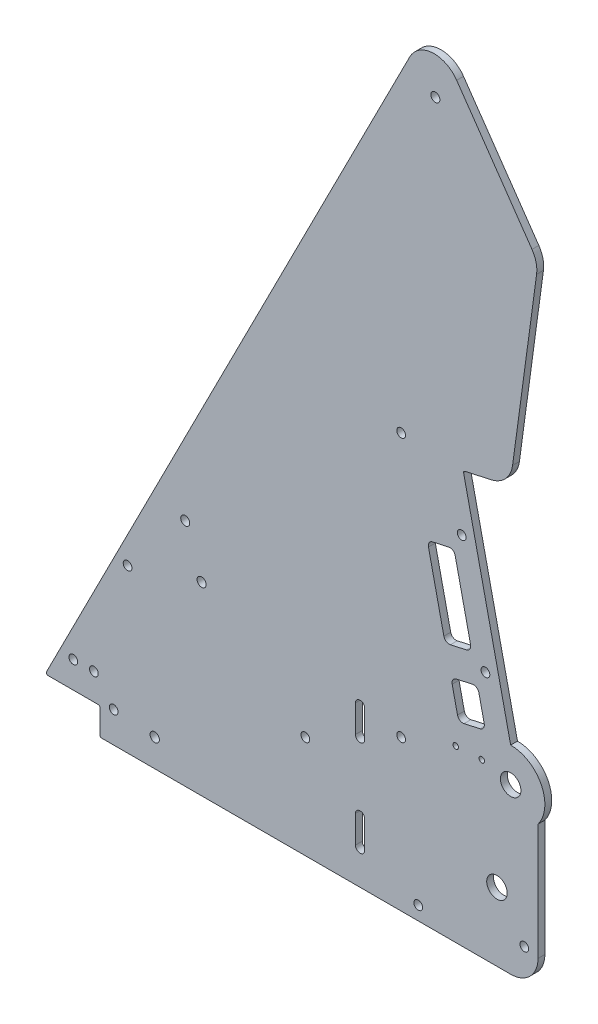
SolidWorks part; units mm, degrees
other "Markup1"
sketch "Sketch5"
ref_plane "Front Plane" through (0, 0, 0) normal (0, 0, 1) x (1, 0, 0)
ref_plane "Top Plane" through (0, 0, 0) normal (0, 1, 0) x (1, 0, 0)
ref_plane "Right Plane" through (0, 0, 0) normal (1, 0, 0) x (0, 0, -1)
sketch "Sketch1" plane through (0, 0, 0) normal (0, 0, 1) x (1, 0, 0)
  line L1 (228.6, -12.7) -> (228.6, 53.975)
  line L2 (178.7547, 351.4131) -> (0, 0)
  line L3 (228.6, 279.4) -> (178.7547, 351.4131)
  line L5 (0, 0) -> (25.4, 0)
  line L6 (25.4, 0) -> (25.4, -12.7)
  line L7 (25.4, -12.7) -> (228.6, -12.7)
  line L9 (215.9, 79.375) -> (193.9097, 178.5667)
  line L10 (193.9097, 178.5667) -> (215.6079, 183.377)
  line L11 (215.6079, 183.377) -> (228.6, 279.4)
  arc A0 (228.6, 53.975) -> (215.9, 79.375) centre (215.9, 63.5) ccw
  dimension "D7" = 12.7
  dimension "D8" = 76.2
  dimension "D10" = 31.75
  dimension "D2" = 292.1
  dimension "D3" = 25.4
  dimension "D4" = 215.9
  dimension "D5" = 394.2644
  dimension "D6" = 203.2
  dimension "D9" = 63.039
  dimension "D11" = 101.6
  dimension "D12" = 12.5
  dimension "D13" = 22.225
extrude "Boss-Extrude1" add sketch "Sketch1" along normal blind 3.175
sketch "Sketch2" plane through (0, 0, 3.175) normal (0, 0, 1) x (1, 0, 0)
  line L0 (178.7547, 351.4131) -> (0, 0) construction
  line L1 (25.4, -12.7) -> (228.6, -12.7) construction
  line L2 (215.9, 79.375) -> (193.9097, 178.5667) construction
  line L3 (193.9097, 178.5667) -> (215.6079, 183.377) construction
  line L4 (215.9, 79.375) -> (193.9097, 178.5667) construction
  line L5 (64.9432, 94.0578) -> (72.5445, 73.1732) construction
  line L6 (64.9432, 94.0578) -> (89.8317, 94.0578) construction
  line L10 (228.6, -12.7) -> (228.6, 53.975) construction
  circle A0 centre (64.9432, 94.0578) radius 2.0955
  circle A1 centre (180.975, 322.1643) radius 2.0955
  circle A2 centre (72.5445, 73.1732) radius 2.0955
  circle A3 centre (193.2078, 152.3944) radius 2.032
  circle A4 centre (215.9, 63.5) radius 4.7625
  circle A7 centre (173.0375, -6.35) radius 2.032
  circle A8 centre (204.203, 102.7985) radius 2.032
  circle A26 centre (209.55, 19.05) radius 4.7625
  arc A30 (228.6, 53.975) -> (215.9, 79.375) centre (215.9, 63.5) ccw construction
  circle A31 centre (165.1, 179.3875) radius 2.032
  dimension "D3" = 4.191
  dimension "D5" = 4.191
  dimension "D9" = 4.191
  dimension "D20" = 9.525
  dimension "D23" = 9.525
  dimension "D18" = 4.064
  dimension "D26" = 4.064
  dimension "D14" = 4.064
  dimension "D2" = 15.24
  dimension "D6" = 15.24
  dimension "D7" = 22.225
  dimension "D21" = 44.45
  dimension "D22" = 6.35
  dimension "D19" = 160.3375
  dimension "D24" = 44.45
  dimension "D25" = 6.35
  dimension "D27" = 25.4
  dimension "D28" = 50.8
  dimension "D29" = 6.35
  dimension "D17" = 6.35
  dimension "D33" = 55.5625
  dimension "D15" = 114.3
  dimension "D4" = 180.975
  dimension "D8" = 70
extrude "Cut-Extrude1" cut sketch "Sketch2" against normal through all
sketch "Sketch7" plane through (0, 0, 3.175) normal (0, 0, 1) x (1, 0, 0)
  line L0 (146.05, 3.175) -> (146.05, 15.875) construction
  line L1 (143.891, 3.175) -> (143.891, 15.875)
  line L2 (148.209, 3.175) -> (148.209, 15.875)
  line L3 (146.05, 47.625) -> (146.05, 60.325) construction
  line L4 (143.891, 47.625) -> (143.891, 60.325)
  line L5 (148.209, 47.625) -> (148.209, 60.325)
  line L6 (25.4, -12.7) -> (228.6, -12.7) construction
  line L12 (228.6, -12.7) -> (228.6, 53.975) construction
  line L13 (25.4, -12.7) -> (228.6, -12.7) construction
  arc A0 (143.891, 3.175) -> (148.209, 3.175) centre (146.05, 3.175) ccw
  arc A1 (148.209, 15.875) -> (143.891, 15.875) centre (146.05, 15.875) ccw
  arc A2 (143.891, 47.625) -> (148.209, 47.625) centre (146.05, 47.625) ccw
  arc A3 (148.209, 60.325) -> (143.891, 60.325) centre (146.05, 60.325) ccw
  circle A8 centre (50.8, 0) radius 2.159
  point P2 (146.05, 9.525)
  point P9 (146.05, 53.975)
  dimension "D1" = 4.318
  dimension "D5" = 4.318
  dimension "D2" = 12.7
  dimension "D3" = 12.7
  dimension "D4" = 44.45
  dimension "D6" = 95.25
  dimension "D7" = 82.55
  dimension "D8" = 15.875
  dimension "D9" = 12.7
extrude "Cut-Extrude2" cut sketch "Sketch7" against normal through all
sketch "Sketch10" plane through (0, 0, 3.175) normal (0, 0, 1) x (1, 0, 0)
  circle A1 centre (165.1, 57.15) radius 2.032
  circle A2 centre (120.65, 34.925) radius 2.032
  circle A3 centre (13.0465, 12.3347) radius 2.032
  circle A4 centre (22.5715, 12.3347) radius 2.032
  circle A5 centre (38.2114, 62.6398) radius 2.032
  dimension "D1" = 4.064
  dimension "D2" = 4.064
  dimension "D4" = 63.5
  dimension "D5" = 69.85
extrude "Cut-Extrude3" cut sketch "Sketch10" against normal up to next
fillet "Fillet1" radius 12.7 4 edges at (228.6, -12.7, 1.5875) (178.7547, 351.4131, 1.5875) (215.6079, 183.377, 1.5875) (228.6, 279.4, 1.5875)
fillet "Fillet2" radius 0.7937 4 edges at (25.4, -12.7, 1.5875) (25.4, 0, 1.5875) (193.9097, 178.5667, 1.5875) (0, 0, 1.5875)
sketch "Sketch12" plane through (0, 0, 3.175) normal (0, 0, 1) x (1, 0, 0)
  circle A0 centre (31.75, 1.5875) radius 2.032
  circle A1 centre (222.25, 1.5875) radius 2.032
  dimension "D1" = 4.064
extrude "Cut-Extrude5" cut sketch "Sketch12" against normal through all
sketch "Sketch13" plane through (0, 0, 3.175) normal (0, 0, 1) x (1, 0, 0)
  line L0 (189.6226, 145.0954) -> (197.869, 107.8985)
  line L1 (177.2237, 142.3466) -> (185.47, 105.1497)
  line L2 (215.9, 79.375) -> (194.0815, 177.7917) construction
  line L3 (185.47, 105.1497) -> (197.869, 107.8985)
  line L4 (177.2237, 142.3466) -> (189.6226, 145.0954)
  line L5 (194.6847, 178.7385) -> (206.9592, 181.4597) construction
  line L6 (190.4268, 66.2609) -> (202.5335, 66.7895) construction
  line L7 (188.2188, 92.7508) -> (200.6178, 95.4995)
  line L8 (188.2188, 92.7508) -> (191.7922, 76.6321)
  line L9 (191.7922, 76.6321) -> (204.1912, 79.3809)
  line L10 (200.6178, 95.4995) -> (204.1912, 79.3809)
  line L11 (190.4268, 66.2609) -> (191.7922, 76.6321) construction
  line L12 (202.5335, 66.7895) -> (204.1912, 79.3809) construction
  circle A0 centre (190.4268, 66.2609) radius 1.27
  circle A1 centre (202.5335, 66.7895) radius 1.27
  point P3 (193.7458, 126.4969)
  point P6 (181.3468, 123.7481)
  dimension "D7" = 2.54
  dimension "D1" = 38.1
  dimension "D2" = 12.7
  dimension "D3" = 11.43
  dimension "D4" = 50.8
  dimension "D5" = 16.51
  dimension "D6" = 12.7
  dimension "D8" = 110
  dimension "D9" = 80
  dimension "D10" = 12.7
extrude "Cut-Extrude6" cut sketch "Sketch13" against normal through all both and the other way through all
fillet "Fillet3" radius 2.54 8 edges at (177.2237, 142.3466, 1.5875) (189.6226, 145.0954, 1.5875) (197.869, 107.8985, 1.5875) (185.47, 105.1497, 1.5875) (200.6178, 95.4995, 1.5875) (188.2188, 92.7508, 1.5875) (191.7922, 76.6321, 1.5875) (204.1912, 79.3809, 1.5875)
equation "\"D6@Sketch2\"=\"D2@Sketch2\""
